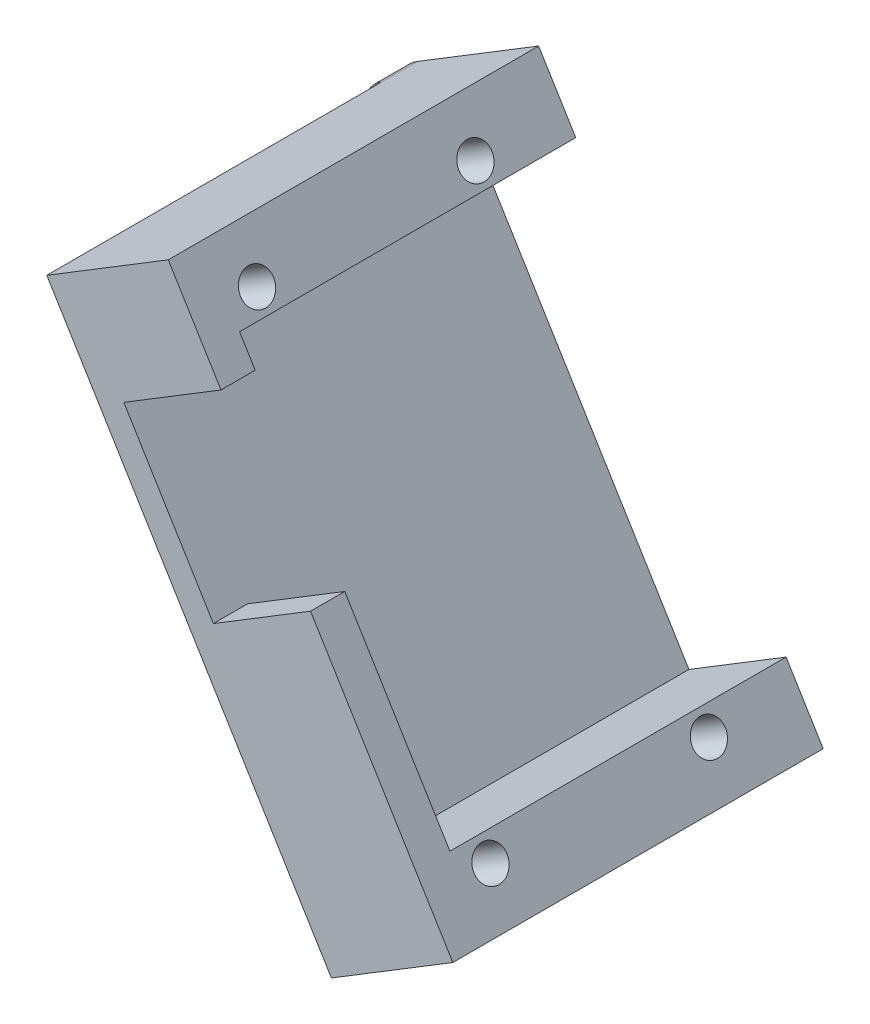
SolidWorks part; units mm, degrees
ref_plane "Front Plane" through (0, 0, 0) normal (0, 0, 1) x (1, 0, 0)
ref_plane "Top Plane" through (0, 0, 0) normal (0, 1, 0) x (1, 0, 0)
ref_plane "Right Plane" through (0, 0, 0) normal (1, 0, 0) x (0, 0, -1)
sketch "Sketch2" plane through (0, 0, 0) normal (0, 0, 1) x (1, 0, 0)
  line L0 (-38.8523, 46.0124) -> (-20.099, 15.2827)
  line L1 (-20.099, 15.2827) -> (-3.027, 25.7013)
  line L2 (-3.027, 25.7013) -> (-21.7803, 56.4309)
  line L3 (-21.7803, 56.4309) -> (-38.8523, 46.0124)
  line L4 (-47.5806, 48.1249) -> (-22.2115, 6.5545)
  line L5 (-22.2115, 6.5545) -> (5.7013, 23.5888)
  line L6 (5.7013, 23.5888) -> (-19.6678, 65.1592)
  line L7 (-19.6678, 65.1592) -> (-47.5806, 48.1249)
  dimension "D1" = 6.35
extrude "Boss-Extrude1" add sketch "Sketch2" along normal blind 3.048
sketch "Sketch3" plane through (0, 0, 3.048) normal (0, 0, 1) x (1, 0, 0)
  line L0 (-38.8523, 46.0124) -> (-20.099, 15.2827)
  line L1 (-20.099, 15.2827) -> (-3.027, 25.7013)
  line L2 (-3.027, 25.7013) -> (-21.7803, 56.4309)
  line L3 (-21.7803, 56.4309) -> (-38.8523, 46.0124)
  line L4 (2.4491, 21.6041) -> (-22.92, 63.1745)
  line L5 (-44.3284, 50.1096) -> (-18.9593, 8.5392)
  line L6 (-44.3284, 50.1096) -> (-22.92, 63.1745)
  line L8 (-41.0205, 44.6893) -> (-22.2671, 13.9596) construction
  line L9 (-0.8588, 27.0244) -> (-19.6122, 57.7541) construction
  line L10 (-18.9593, 8.5392) -> (2.4491, 21.6041)
  point P17 (-33.6242, 56.642)
  point P20 (-8.2551, 15.0716)
  dimension "D1" = 2.54
extrude "Boss-Extrude2" add sketch "Sketch3" along normal blind 29.972
sketch "Sketch4" plane through (0, 0, 33.02) normal (0, 0, 1) x (1, 0, 0)
  line L0 (-38.8523, 46.0124) -> (-37.4613, 43.733)
  line L1 (-38.8523, 46.0124) -> (-20.099, 15.2827) construction
  line L2 (-37.4613, 43.733) -> (-20.3893, 54.1516)
  line L3 (-3.027, 25.7013) -> (-21.7803, 56.4309) construction
  line L4 (-20.3893, 54.1516) -> (-21.7803, 56.4309)
  line L5 (-21.7803, 56.4309) -> (-38.8523, 46.0124)
  line L6 (-29.4757, 30.6476) -> (-12.4036, 41.0661)
  line L7 (-12.4036, 41.0661) -> (-3.027, 25.7013)
  line L8 (-3.027, 25.7013) -> (-20.099, 15.2827)
  line L9 (-20.099, 15.2827) -> (-29.4757, 30.6476)
extrude "Boss-Extrude3" add sketch "Sketch4" against normal blind 3.048
sketch "Sketch12" plane through (0, 0, 3.048) normal (0, 0, 1) x (1, 0, 0)
  line L0 (2.4491, 21.6041) -> (5.7013, 23.5888)
  line L1 (5.7013, 23.5888) -> (8.1204, 25.0651)
  line L2 (8.1204, 25.0651) -> (-17.2487, 66.6355)
  line L3 (-17.2487, 66.6355) -> (-22.92, 63.1745)
  line L4 (-22.92, 63.1745) -> (2.4491, 21.6041)
extrude "Boss-Extrude4" add sketch "Sketch12" against normal blind 3.048
sketch "Sketch13" plane through (11.391, 6.9516, 0) normal (0.8536, 0.5209, 0) x (0, 0, -1)
  line L1 (-33.02, 65.8655) -> (-3.048, 65.8655)
  line L2 (-33.02, 65.8655) -> (-33.02, 17.1655)
  line L3 (-33.02, 17.1655) -> (-3.048, 17.1655)
  line L4 (-3.048, 65.8655) -> (-3.048, 17.1655)
extrude "Boss-Extrude5" add sketch "Sketch13" along normal blind 3.048
hole_wizard "CSK for #4 Flat Head Machine Screw (100)2" positions "Sketch10" profile "Sketch11" countersink size "#4" standard "ANSI Inch" end condition through all
sketch "Sketch10" plane through (-10.0173, -6.1133, 0) normal (-0.8536, -0.5209, 0) x (0, 0, 1)
  point P0 (27.3976, 61.4714)
  point P2 (7.9259, 61.4714)
  point P4 (7.9259, 21.5155)
  point P6 (27.3976, 21.5155)
sketch "Sketch11" plane through (-42.0394, 46.3589, 27.3976) normal (0, 0, 1) x (0.5209, -0.8536, 0)
  line L0 (0, 0) -> (0, 53.3792)
  line L1 (0, 53.3792) -> (1.4732, 53.3792)
  line L2 (1.4732, 53.3792) -> (1.4732, 1.1616)
  line L3 (1.4732, 1.1616) -> (2.8575, 0)
  line L5 (2.8575, 0) -> (0, 0)
  line L6 (-1.4732, 1.1616) -> (-2.8575, 0) construction
  line L11 (0, -6.35) -> (0, 107.95) construction
  dimension "Thru Hole Dia." = 2.9464
  dimension "Thru Hole Depth" = 53.3792
  dimension "Near C'Sink Dia." = 5.715
  dimension "Near C'Sink Angle" = 100
ref_plane "Plane1" through (11.6078, 7.0839, 0) normal (0.8536, 0.5209, 0) x (0, 0, -1)
sketch "Sketch14" plane through (11.6078, 7.0839, 0) normal (0.8536, 0.5209, 0) x (0, 0, -1)
  line L0 (-30.6972, 19.6105) -> (-30.6972, 14.9798)
  line L1 (-27.3976, 57.6614) -> (-24.0981, 59.5664)
  line L2 (-24.0981, 59.5664) -> (-24.0981, 63.3764)
  line L5 (-30.6972, 63.3764) -> (-30.6972, 59.5664)
  line L6 (-30.6972, 59.5664) -> (-27.3976, 57.6614)
  line L7 (-7.9259, 57.6614) -> (-4.6264, 59.5664)
  line L8 (-4.6264, 59.5664) -> (-4.6264, 63.3764)
  line L11 (-11.2255, 63.3764) -> (-11.2255, 59.5664)
  line L12 (-11.2255, 59.5664) -> (-7.9259, 57.6614)
  line L13 (-7.9259, 25.3255) -> (-11.2255, 23.4205)
  line L14 (-11.2255, 23.4205) -> (-11.2255, 19.6105)
  line L17 (-4.6264, 19.6105) -> (-4.6264, 23.4205)
  line L18 (-4.6264, 23.4205) -> (-7.9259, 25.3255)
  line L19 (-27.3976, 25.3255) -> (-30.6972, 23.4205)
  line L20 (-30.6972, 23.4205) -> (-30.6972, 19.6105)
  line L23 (-24.0981, 19.6105) -> (-24.0981, 23.4205)
  line L24 (-24.0981, 23.4205) -> (-27.3976, 25.3255)
  line L25 (-30.6972, 14.9798) -> (-24.0981, 14.9798)
  line L26 (-24.0981, 14.9798) -> (-24.0981, 19.6105)
  line L27 (-11.2255, 19.6105) -> (-11.2255, 14.9798)
  line L28 (-11.2255, 14.9798) -> (-4.6264, 14.9798)
  line L29 (-4.6264, 14.9798) -> (-4.6264, 19.6105)
  line L30 (-4.6264, 63.3764) -> (-4.6264, 70.9964)
  line L31 (-4.6264, 70.9964) -> (-11.2255, 70.9964)
  line L32 (-11.2255, 70.9964) -> (-11.2255, 63.3764)
  line L33 (-24.0981, 63.3764) -> (-24.0981, 70.9964)
  line L34 (-24.0981, 70.9964) -> (-30.6972, 70.9964)
  line L35 (-30.6972, 70.9964) -> (-30.6972, 63.3764)
  line L37 (-27.3976, 65.2814) -> (-29.0474, 64.3289) [skipped]
  line L38 (-25.7478, 64.3289) -> (-27.3976, 65.2814) [skipped]
  line L39 (-6.2761, 64.3289) -> (-7.9259, 65.2814) [skipped]
  line L40 (-7.9259, 65.2814) -> (-9.5757, 64.3289) [skipped]
  line L41 (-9.5757, 18.658) -> (-7.9259, 17.7055) [skipped]
  line L42 (-6.2761, 18.658) -> (-4.6264, 19.6105) [skipped]
  line L43 (-30.6972, 19.6105) -> (-29.0474, 18.658) [skipped]
  line L44 (-25.7478, 18.658) -> (-24.0981, 19.6105) [skipped]
  arc A4 (-30.6972, 61.4714) -> (-24.0981, 61.4714) centre (-27.3976, 61.4714) ccw construction
  arc A5 (-11.2255, 61.4714) -> (-4.6264, 61.4714) centre (-7.9259, 61.4714) ccw construction
  arc A6 (-4.6264, 21.5155) -> (-11.2255, 21.5155) centre (-7.9259, 21.5155) ccw construction
  arc A7 (-24.0981, 21.5155) -> (-30.6972, 21.5155) centre (-27.3976, 21.5155) ccw construction
extrude "Cut-Extrude1" cut sketch "Sketch14" against normal blind 1.397 and the other way blind 1.397
sketch "Sketch15" plane through (0, 0, 0) normal (0, 0, -1) x (-1, 0, 0)
  line L0 (-8.1204, 25.0651) -> (17.2487, 66.6355) construction
  line L1 (47.5806, 48.1249) -> (22.2115, 6.5545) construction
  circle A0 centre (9.7581, 54.3612) radius 9.184
  circle A1 centre (39.9278, 35.5849) radius 8.1247
  circle A2 centre (25.6104, 18.0464) radius 8.2015
  circle A3 centre (-3.4576, 32.7057) radius 5.8102
extrude "Boss-Extrude6" add sketch "Sketch15" against normal blind 3.048
hole_wizard "CSK for #4 Flat Head Machine Screw1" positions "Sketch18" profile "Sketch19" countersink size "#4" standard "ANSI Inch" end condition through all
sketch "Sketch18" plane through (0, 0, 3.048) normal (0, 0, 1) x (1, 0, 0)
  point P0 (3.7644, 32.8603)
  point P2 (-26.4116, 14.2104)
  point P4 (-39.8451, 35.7872)
  point P6 (-9.297, 54.2582)
sketch "Sketch19" plane through (3.7644, 32.8603, 3.048) normal (1, 0, 0) x (0, -1, 0)
  line L0 (0, 0) -> (0, 3.048)
  line L1 (0, 3.048) -> (1.4732, 3.048)
  line L2 (1.4732, 3.048) -> (1.4732, 1.5925)
  line L3 (1.4732, 1.5925) -> (2.8575, 0)
  line L5 (2.8575, 0) -> (0, 0)
  line L6 (-1.4732, 1.5925) -> (-2.8575, 0) construction
  line L11 (0, -6.35) -> (0, 107.95) construction
  dimension "Thru Hole Dia." = 2.9464
  dimension "Thru Hole Depth" = 3.048
  dimension "Near C'Sink Dia." = 5.715
  dimension "Near C'Sink Angle" = 82
sketch "Sketch20" plane through (0, 0, 0) normal (0, 0, -1) x (-1, 0, 0)
  line L0 (14.5423, 62.2008) -> (11.564, 57.3204)
  line L1 (21.7803, 56.4309) -> (38.8523, 46.0124)
  line L2 (38.8523, 46.0124) -> (20.099, 15.2827)
  line L3 (20.099, 15.2827) -> (3.027, 25.7013)
  line L4 (3.027, 25.7013) -> (21.7803, 56.4309)
  line L5 (14.5423, 62.2008) -> (14.5423, 65.1603)
  line L6 (14.5423, 65.1603) -> (8.559, 68.8117)
  line L7 (8.559, 68.8117) -> (-14.062, 31.7445)
  line L8 (-14.062, 31.7445) -> (-6.7627, 27.29)
  line L9 (-8.1204, 25.0651) -> (-6.4843, 27.7461) construction
  line L10 (-6.7627, 27.29) -> (-6.4843, 27.7461)
  line L11 (22.2115, 6.5545) -> (24.782, 10.7665)
  line L12 (47.5806, 48.1249) -> (51.8017, 35.7872)
  line L13 (51.8017, 35.7872) -> (47.5768, 5.2277)
  line L14 (47.5768, 5.2277) -> (22.2115, 6.5545)
  line L15 (7.6103, 50.8419) -> (-1.4954, 35.921)
  line L16 (-5.4488, 29.4429) -> (-6.4843, 27.7461)
  line L17 (28.7292, 17.2345) -> (38.0127, 32.4468)
  line L18 (41.9779, 38.9443) -> (47.5806, 48.1249)
  arc A0 (-1.4954, 35.921) -> (-5.4488, 29.4429) centre (-3.7644, 32.8603) ccw
  arc A1 (11.564, 57.3204) -> (7.6103, 50.8419) centre (9.297, 54.2582) ccw
  arc A2 (38.0127, 32.4468) -> (41.9779, 38.9443) centre (39.8451, 35.7872) ccw
  arc A3 (24.782, 10.7665) -> (28.7292, 17.2345) centre (26.4116, 14.2104) ccw
  circle A4 centre (0, 0) radius 69.342 construction
extrude "Cut-Extrude2" cut sketch "Sketch20" against normal blind 3.048
fillet "Fillet3" radius 3.81 4 edges at (-17.2487, 66.6355, 1.524) (-47.5806, 48.1249, 1.524) (-22.2115, 6.5545, 1.524) (8.1204, 25.0651, 1.524)
fillet "Fillet4" radius 1.27 7 edges at (-24.782, 10.7665, 1.524) (-28.7292, 17.2345, 1.524) (-38.0127, 32.4468, 1.524) (-41.9779, 38.9443, 1.524) (-11.564, 57.3204, 1.524) (-7.6103, 50.8419, 1.524) (1.4954, 35.921, 1.524)
sketch "Sketch21" plane through (-8.9419, 14.6525, 0) normal (0.5209, -0.8536, 0) x (0.8536, 0.5209, 0)
  line L0 (-11.7353, 33.02) -> (16.1787, 33.02) construction
  line L1 (2.2217, 33.02) -> (2.2217, 0) construction
  line L2 (-11.7353, 0) -> (16.1787, 0) construction
  line L4 (0.9517, 33.02) -> (3.4917, 33.02)
  line L5 (0.9517, 33.02) -> (0.9517, 0)
  line L6 (0.9517, 0) -> (3.4917, 0)
  line L7 (3.4917, 33.02) -> (3.4917, 0)
  line L8 (0.9517, 33.02) -> (3.4917, 0) construction
  line L9 (0.9517, 0) -> (3.4917, 33.02) construction
  point P8 (2.2217, 16.51)
  dimension "D1" = 2.54
extrude "Cut-Extrude3" cut sketch "Sketch21" against normal blind 77.47
fillet "Fillet5" radius 0.508 1 edges at (-31.6438, 29.3244, 3.048)
fillet "Fillet6" radius 0.508 1 edges at (-7.6337, 43.977, 3.048)
ref_plane "Plane2" through (2.068, 1.262, 0) normal (0.8536, 0.5209, 0) x (0, 0, -1)
sketch "Sketch22" plane through (2.068, 1.262, 0) normal (0.8536, 0.5209, 0) x (0, 0, -1)
  line L1 (-104.2124, 141.8108) -> (18.8373, 141.8108)
  line L2 (-104.2124, 141.8108) -> (-104.2124, 7.0976)
  line L3 (-104.2124, 7.0976) -> (18.8373, 7.0976)
  line L4 (18.8373, 141.8108) -> (18.8373, 7.0976)
  line L5 (-104.2124, 141.8108) -> (18.8373, 7.0976) construction
  line L6 (-104.2124, 7.0976) -> (18.8373, 141.8108) construction
  point P0 (-42.6876, 74.4542)
extrude "Cut-Extrude4" cut sketch "Sketch22" along normal blind 61.722
